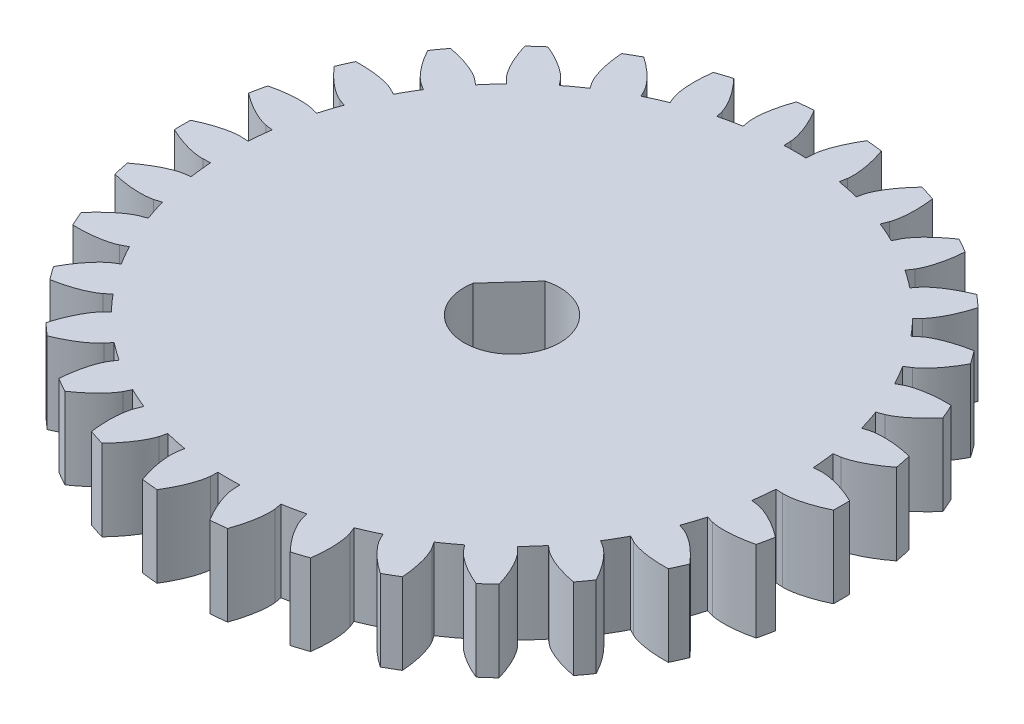
SolidWorks part; units mm, degrees
other "Markup1"
sketch "Sketch3" plane through (20.32, 5, -20.2548) normal (0.411, 0.909, -0.0688) x (0.9086, -0.4023, 0.1126)
ref_plane "Front Plane" through (0, 0, 0) normal (0, 0, 1) x (1, 0, 0)
ref_plane "Top Plane" through (0, 0, 0) normal (0, 1, 0) x (1, 0, 0)
ref_plane "Right Plane" through (0, 0, 0) normal (1, 0, 0) x (0, 0, -1)
ref_plane "Bottom Plane" through (0, 0, 0) normal (0, 1, 0) x (1, 0, 0)
sketch "Sketch1" plane through (0, 0, 0) normal (0, 1, 0) x (1, 0, 0)
  line L0 (0, 0) -> (-0.695, 17.8876)
  line L1 (0, 0) -> (0.695, 17.8876)
  line L2 (0, 0) -> (0, 20.32) construction
  line L3 (0, 0) -> (0.997, 19.0239) construction
  line L4 (0, 0) -> (-0.997, 19.0239) construction
  circle A0 centre (0, 0) radius 19.05 construction
  circle A1 centre (0, 0) radius 17.9011 construction
  circle A2 centre (0, 0) radius 20.32
  circle A3 centre (0, 0) radius 17.4625
  circle A4 centre (0, 0) radius 2.95
  spline S0 degree 4 poles (0.695, 17.8876) (0.6955, 17.9009) (0.6978, 17.9379) (0.7056, 18.0078) (0.7231, 18.1212) (0.7525, 18.2647) (0.7986, 18.4486) (0.8631, 18.6631) (0.9447, 18.896) (1.0449, 19.1459) (1.1548, 19.3919) (1.2735, 19.634) (1.3999, 19.8718) (1.5626, 20.1557) (1.7707, 20.4902) (2.0326, 20.8717) (2.3512, 21.2925) (2.6983, 21.7077) (3.058, 22.1046) (3.4414, 22.4913) (3.8265, 22.8552) (4.2459, 23.2174) (4.643, 23.5437) (5.1082, 23.8908) (5.4897, 24.1655) (6.0135, 24.5074) (6.329, 24.703) (6.7049, 24.9247) (6.8754, 25.0192) (6.9802, 25.0775) knots 0 0 0 0 0 0.005377 0.015084 0.028532 0.04661 0.064855 0.092111 0.119476 0.146842 0.174209 0.201575 0.228941 0.256307 0.307035 0.361767 0.4165 0.471232 0.525964 0.580697 0.635429 0.690161 0.744894 0.799626 0.854358 0.909091 0.954545 1 1 1 1 1 construction
  spline S1 degree 4 poles (0.695, 17.8876) (0.6955, 17.9009) (0.6978, 17.9379) (0.7056, 18.0078) (0.7231, 18.1212) (0.7525, 18.2647) (0.7986, 18.4486) (0.8631, 18.6631) (0.9447, 18.896) (1.0449, 19.1459) (1.1548, 19.3919) (1.2735, 19.634) (1.3999, 19.8718) (1.5626, 20.1557) (1.7707, 20.4902) (2.0326, 20.8717) (2.3512, 21.2925) (2.6983, 21.7077) (3.058, 22.1046) (3.4414, 22.4913) (3.8265, 22.8552) (4.2459, 23.2174) (4.643, 23.5437) (5.1082, 23.8908) (5.4897, 24.1655) (5.9, 24.4332) (6.102, 24.5611) (6.2062, 24.6255) knots 0 0 0 0 0 0.005377 0.015084 0.028532 0.04661 0.064855 0.092111 0.119476 0.146842 0.174209 0.201575 0.228941 0.256307 0.307035 0.361767 0.4165 0.471232 0.525964 0.580697 0.635429 0.690161 0.744894 0.799626 0.854358 0.909091 0.909091 0.909091 0.909091 0.909091
  spline S2 degree 4 poles (-0.695, 17.8876) (-0.6955, 17.9009) (-0.6978, 17.9379) (-0.7056, 18.0078) (-0.7231, 18.1212) (-0.7525, 18.2647) (-0.7986, 18.4486) (-0.8631, 18.6631) (-0.9447, 18.896) (-1.0449, 19.1459) (-1.1548, 19.3919) (-1.2735, 19.634) (-1.3999, 19.8718) (-1.5626, 20.1557) (-1.7707, 20.4902) (-2.0326, 20.8717) (-2.3512, 21.2925) (-2.6983, 21.7077) (-3.058, 22.1046) (-3.4414, 22.4913) (-3.8265, 22.8552) (-4.2459, 23.2174) (-4.643, 23.5437) (-5.1082, 23.8908) (-5.4897, 24.1655) (-6.0135, 24.5074) (-6.329, 24.703) (-6.7049, 24.9247) (-6.8754, 25.0192) (-6.9802, 25.0775) knots 0 0 0 0 0 0.005377 0.015084 0.028532 0.04661 0.064855 0.092111 0.119476 0.146842 0.174209 0.201575 0.228941 0.256307 0.307035 0.361767 0.4165 0.471232 0.525964 0.580697 0.635429 0.690161 0.744894 0.799626 0.854358 0.909091 0.954545 1 1 1 1 1 construction
  spline S3 degree 4 poles (-0.695, 17.8876) (-0.6955, 17.9009) (-0.6978, 17.9379) (-0.7056, 18.0078) (-0.7231, 18.1212) (-0.7525, 18.2647) (-0.7986, 18.4486) (-0.8631, 18.6631) (-0.9447, 18.896) (-1.0449, 19.1459) (-1.1548, 19.3919) (-1.2735, 19.634) (-1.3999, 19.8718) (-1.5626, 20.1557) (-1.7707, 20.4902) (-2.0326, 20.8717) (-2.3512, 21.2925) (-2.6983, 21.7077) (-3.058, 22.1046) (-3.4414, 22.4913) (-3.8265, 22.8552) (-4.2459, 23.2174) (-4.643, 23.5437) (-5.1082, 23.8908) (-5.4897, 24.1655) (-5.9, 24.4332) (-6.102, 24.5611) (-6.2062, 24.6255) knots 0 0 0 0 0 0.005377 0.015084 0.028532 0.04661 0.064855 0.092111 0.119476 0.146842 0.174209 0.201575 0.228941 0.256307 0.307035 0.361767 0.4165 0.471232 0.525964 0.580697 0.635429 0.690161 0.744894 0.799626 0.854358 0.909091 0.909091 0.909091 0.909091 0.909091
  dimension "D1" = 38.1
  dimension "D2" = 35.8023
  dimension "D7" = 5.9
  dimension "D3" = 1.27
  dimension "D4" = 1.5875
  dimension "D5" = 3
  dimension "D6" = 3
extrude "Boss-Extrude1" add sketch "Sketch1" along normal blind 5 contours A2 | A4
extrude "Cut-Extrude1" cut sketch "Sketch1<3>" against normal up to surface from surface contours S3 L0 A3 L1 S1 A2 region at (0, 0, -19.1118) up to face at (0, 0, 20.32) starting at face at (0, 5, 20.32)
sketch "Sketch1<3>" plane through (0, 0, 0) normal (0, 1, 0) x (1, 0, 0) same geometry as "Sketch1"
pattern_circular "CirPattern1" count 30 over 360 about axis through (0, 5, 0) along (0, -1, 0) of "Cut-Extrude1"
sketch "Sketch2" plane through (0, 5, 0) normal (0, 1, 0) x (1, 0, 0)
  line L0 (-2.9055, 0.5107) -> (-0.8083, 2.8371)
  line L2 (-0.7465, 2.9056) -> (-1.8569, 1.6739) construction
  circle A0 centre (0, 0) radius 2.95
  point P0 (0, 0)
  dimension "D1" = 5.9
extrude "Boss-Extrude2" add sketch "Sketch2" against normal blind 5 contours L0 A0 region at (-1.9915, 5, -1.7953)
equation "\"Module\"= 1.270mm'20dp = 1.270mod | 32dp = 0.7938mod"
equation "\"Teeth\"=30"
equation "\"Tooth Width\"= 6mm"
equation "\"Pressure Angle\"= 20deg"
equation "\"D1@Sketch1\"=\"Module\"*\"Teeth\""
equation "\"D2@Sketch1\"=\"D1@Sketch1\"*cos(\"Pressure Angle\")"
equation "\"D3@Sketch1\"=\"Module\""
equation "\"D4@Sketch1\"=1.25*\"Module\""
equation "\"D5@Sketch1\"=360/(\"Teeth\"*4)"
equation "\"D6@Sketch1\"=\"D5@Sketch1\""
equation "\"D1@Boss-Extrude1\"=\"Tooth Width\""
equation "\"D1@CirPattern1\"=\"Teeth\""
equation "\"Teeth\"= 20"
